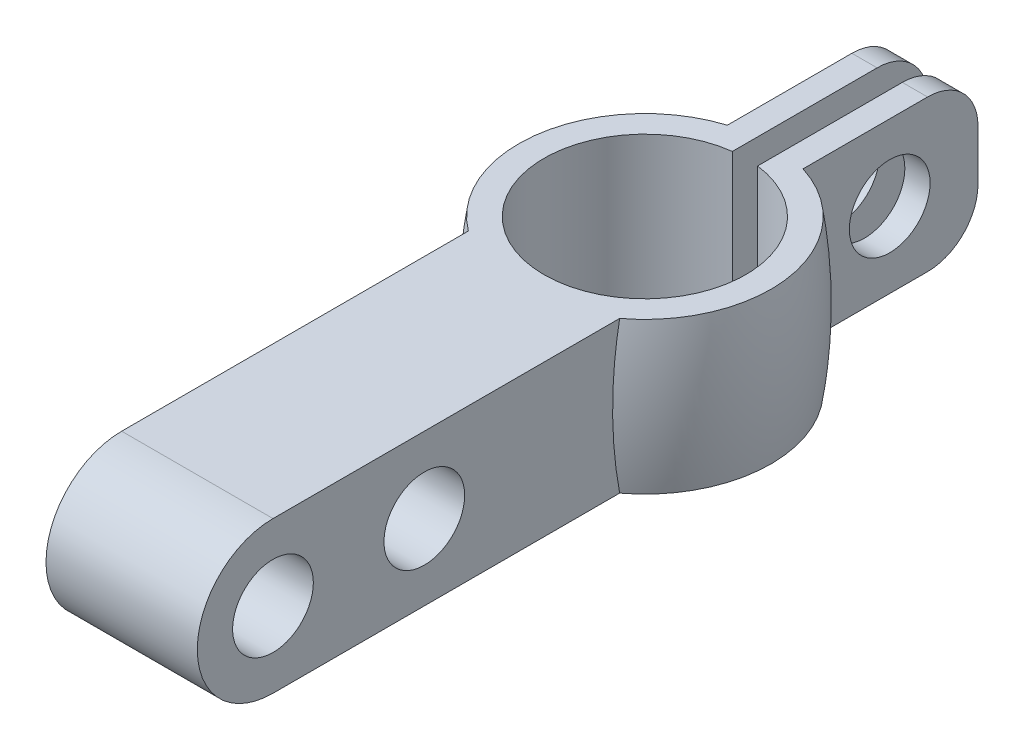
SolidWorks part; units mm, degrees
ref_plane "前视基准面" through (0, 0, 0) normal (0, 0, 1) x (1, 0, 0)
ref_plane "上视基准面" through (0, 0, 0) normal (0, 1, 0) x (1, 0, 0)
ref_plane "右视基准面" through (0, 0, 0) normal (1, 0, 0) x (0, 0, -1)
other "Configuration Table"
sketch "草图1" plane through (0, 0, 0) normal (0, 0, 1) x (1, 0, 0)
  line L0 (0, -4.9233) -> (0, 6.0286) construction
  line L1 (4, 3.9817) -> (4, -2.0183)
  line L2 (4, -2.0183) -> (5, -2.0183)
  line L3 (4, 3.9817) -> (5, 3.9817)
  line L4 (-4.0051, 0.9817) -> (-16.1534, 0.9817) construction
  arc A0 (5, -2.0183) -> (5, 3.9817) centre (-14.7737, 0.9817) ccw
  point P9 (4, 0.9817)
  dimension "D1" = 4
  dimension "D2" = 6
  dimension "D3" = 1
  dimension "D4" = 1
revolve "旋转1" add sketch "草图1" angle 360 about L0
sketch "草图2" plane through (0, 0, 0) normal (0, 1, 0) x (1, 0, 0)
  line L0 (0, -7.3608) -> (0, 8.716) construction
  line L1 (1.5, 6.8306) -> (-1.5, 6.8306)
  line L2 (-1.5, 6.8306) -> (-1.5, 3.2895)
  line L3 (-1.5, 3.2895) -> (1.5, 3.2895)
  line L4 (1.5, 6.8306) -> (1.5, 3.2895)
  point P8 (0, 3.2895)
  point P9 (0, 6.8306)
  dimension "D1" = 3
extrude "切除-拉伸1" cut sketch "草图2" against normal through all and the other way through all
sketch "草图3" plane through (0, 0, 0) normal (0, 1, 0) x (1, 0, 0)
  line L0 (0, -5.921) -> (0, 7.672) construction
  line L1 (-1.5, 3.7081) -> (-0.5, 3.7081)
  line L2 (-0.5, 3.7081) -> (-0.5, 11.7081)
  line L3 (-0.5, 11.7081) -> (-1.5, 11.7081)
  line L4 (-1.5, 11.7081) -> (-1.5, 4.982)
  line L5 (-1.5, 4.982) -> (-1.5, 3.7081)
  line L6 (1.5, 11.7081) -> (1.5, 4.982)
  line L7 (0.5, 11.7081) -> (1.5, 11.7081)
  line L8 (0.5, 3.7081) -> (0.5, 11.7081)
  line L9 (1.5, 3.7081) -> (0.5, 3.7081)
  line L10 (1.5, 4.982) -> (1.5, 3.7081)
  dimension "D1" = 0.5
  dimension "D2" = 8
extrude "凸台-拉伸1" add sketch "草图3" along normal up to surface (3.9817 mm away) and the other way up to surface (2.0183 mm away) up to face at (0, 3.9817, 0.1306) other way up to face at (0, -2.0183, 0.1306)
sketch "草图5" plane through (0, 0, 0) normal (1, 0, 0) x (0, 0, -1)
  line L0 (10.4949, 0.9817) -> (-9.7688, 0.9817) construction
  line L1 (-3.746, 3.9817) -> (-17.746, 3.9817)
  line L2 (3.7081, 3.9817) -> (-4, 3.9817) construction
  line L3 (4.7697, -2.0183) -> (11.7081, -2.0183) construction
  line L4 (-3.746, -2.0183) -> (-17.746, -2.0183)
  line L5 (-3.746, 3.9817) -> (-3.746, -2.0183)
  arc A0 (-17.746, 3.9817) -> (-17.746, -2.0183) centre (-17.746, 0.9817) ccw
  point P8 (-0.146, 3.9817)
  dimension "D1" = 14
  dimension "D2" = 3.6
  dimension "D3" = 3
  dimension "D4" = 3
extrude "凸台-拉伸2" add sketch "草图5" against normal blind 3 and the other way blind 3
sketch "草图6" plane through (3, 0, 0) normal (1, 0, 0) x (0, 0, -1)
  line L0 (11.7081, 3.9817) -> (11.7081, -2.0183) construction
  line L1 (-17.746, 0.9817) -> (8.2081, 0.9817) construction
  circle A0 centre (-17.746, 0.9817) radius 1.6
  circle A1 centre (8.2081, 0.9817) radius 1.6
  circle A2 centre (-11.746, 0.9817) radius 1.6
  dimension "D1" = 3.2
  dimension "D2" = 3.2
  dimension "D4" = 6
  dimension "D5" = 3.2
  dimension "D3" = 3.5
extrude "切除-拉伸2" cut sketch "草图6" against normal through all
sketch "草图7" plane through (0, 3.9817, 0) normal (0, 1, 0) x (1, 0, 0)
  circle A0 centre (0, 0) radius 4
extrude "切除-拉伸3" cut sketch "草图7" against normal through all
fillet "圆角1" radius 2 4 edges at (-1, -2.0183, -11.7081) (-1, 3.9817, -11.7081) (1, -2.0183, -11.7081) (1, 3.9817, -11.7081)
